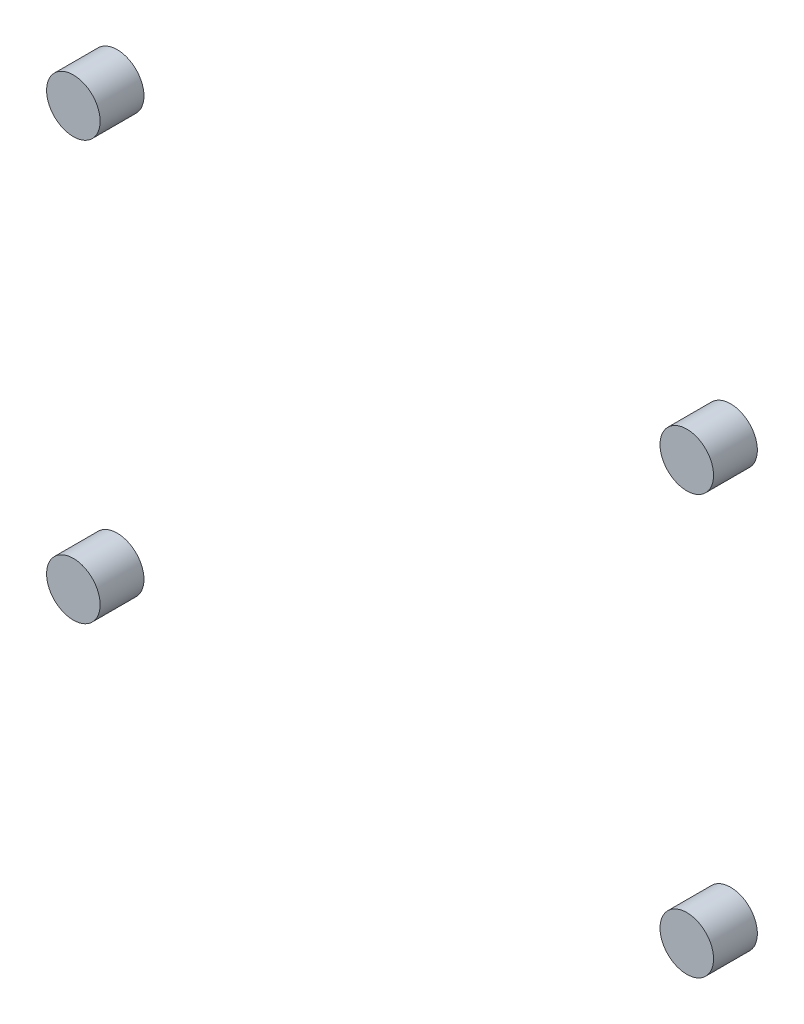
SolidWorks part; units mm, degrees
ref_plane "Front Plane" through (0, 0, 0) normal (0, 0, 1) x (1, 0, 0)
ref_plane "Top Plane" through (0, 0, 0) normal (0, 1, 0) x (1, 0, 0)
ref_plane "Right Plane" through (0, 0, 0) normal (1, 0, 0) x (0, 0, -1)
sketch "Sketch1" plane through (0, 0, 0) normal (0, 1, 0) x (1, 0, 0)
  line L0 (-36, -36) -> (36, -36)
  line L1 (46, -26) -> (46, 26)
  line L2 (36, 36) -> (-36, 36)
  line L3 (-46, 26) -> (-46, -26)
  arc A0 (46, -26) -> (36, -36) centre (36, -26) ccw
  arc A1 (36, 36) -> (46, 26) centre (36, 26) ccw
  arc A2 (-46, 26) -> (-36, 36) centre (-36, 26) ccw
  arc A3 (-36, -36) -> (-46, -26) centre (-36, -26) ccw
sketch "Sketch2" plane through (0, 0, 0) normal (0, 0, 1) x (1, 0, 0)
  circle A0 centre (-31.5, -21.5) radius 2.75
  circle A1 centre (31.5, -21.5) radius 2.75
  circle A2 centre (-31.5, 21.5) radius 2.75
  circle A3 centre (31.5, 21.5) radius 2.75
extrude "Boss-Extrude2" add sketch "Sketch2" along normal blind 4.5
sketch "Sketch3" plane through (0, 0, 0) normal (1, 0, 0) x (0, 0, -1)
  line L1 (-32, 8.5) -> (6, 8.5)
  line L2 (-32, 8.5) -> (-32, 4.5)
  line L3 (-32, 4.5) -> (6, 4.5)
  line L4 (6, 8.5) -> (6, 4.5)
  line L5 (-32, 8.5) -> (6, 4.5) construction
  line L6 (-32, 4.5) -> (6, 8.5) construction
  line L7 (20, 8.5) -> (6, 8.5)
  line L8 (20, 8.5) -> (20, 4.5)
  line L9 (20, 4.5) -> (6, 4.5)
  line L10 (6, 8.5) -> (6, 4.5)
  line L11 (20, 8.5) -> (6, 4.5) construction
  line L12 (20, 4.5) -> (6, 8.5) construction
  point P0 (13, 6.5)
sketch "Sketch4" plane through (0, 0, 0) normal (0, 0, 1) x (1, 0, 0)
  line L1 (29, -44) -> (1, -44)
  line L2 (29, -44) -> (29, 7)
  line L3 (29, 7) -> (1, 7)
  line L4 (1, -44) -> (1, 7)
  line L5 (29, -44) -> (1, 7) construction
  line L6 (29, 7) -> (1, -44) construction
  line L7 (38, -44) -> (1, -44)
  line L8 (38, -44) -> (38, 7)
  line L9 (38, 7) -> (1, 7)
  line L10 (1, -44) -> (1, 7)
  line L11 (38, -44) -> (1, 7) construction
  line L12 (38, 7) -> (1, -44) construction
  line L13 (47, -44) -> (1, -44)
  line L14 (47, -44) -> (47, 7)
  line L15 (47, 7) -> (1, 7)
  line L16 (1, -44) -> (1, 7)
  line L17 (47, -44) -> (1, 7) construction
  line L18 (47, 7) -> (1, -44) construction
  line L19 (57, -44) -> (1, -44)
  line L20 (57, -44) -> (57, 7)
  line L21 (57, 7) -> (1, 7)
  line L22 (1, -44) -> (1, 7)
  line L23 (57, -44) -> (1, 7) construction
  line L24 (57, 7) -> (1, -44) construction
  line L25 (65, -44) -> (1, -44)
  line L26 (65, -44) -> (65, 7)
  line L27 (65, 7) -> (1, 7)
  line L28 (1, -44) -> (1, 7)
  line L29 (65, -44) -> (1, 7) construction
  line L30 (65, 7) -> (1, -44) construction
  point P0 (19.5, -18.5)
  point P5 (24, -18.5)
  point P8 (29, -18.5)
  point P11 (33, -18.5)
